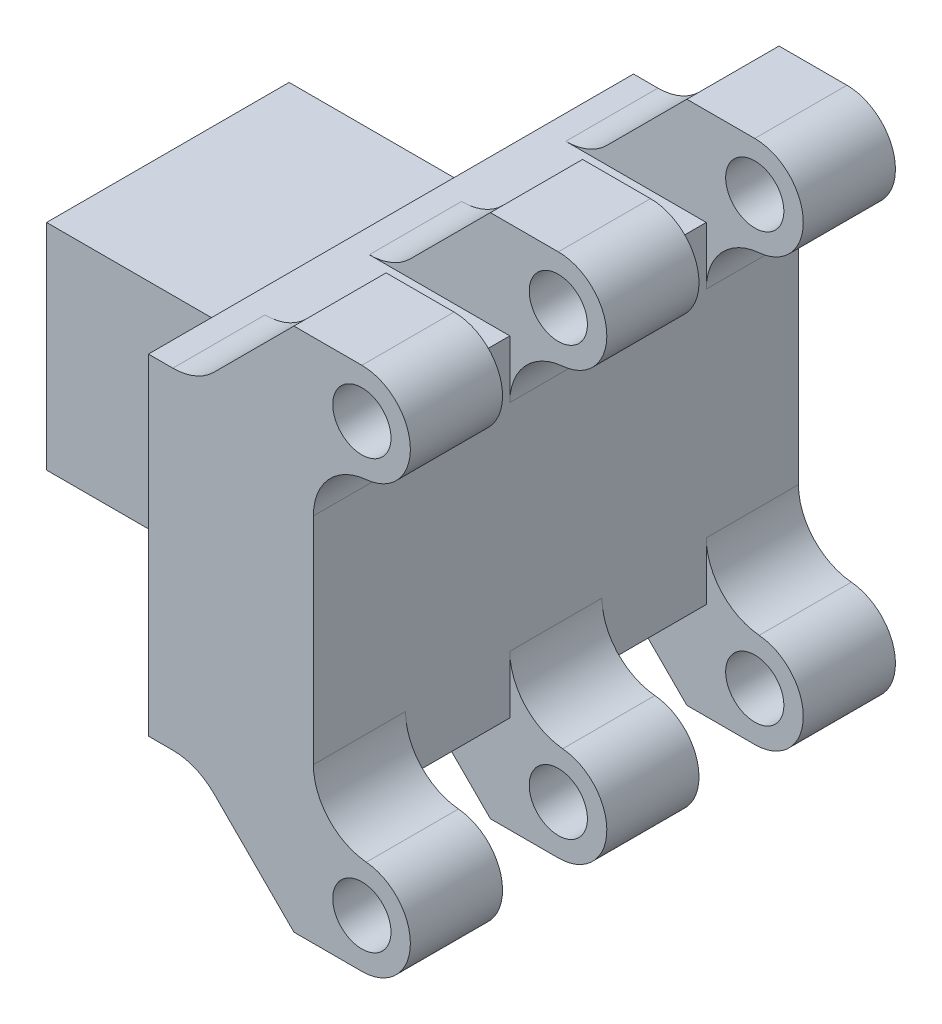
SolidWorks part; units mm, degrees
ref_plane "Front Plane" through (0, 0, 0) normal (0, 0, 1) x (1, 0, 0)
ref_plane "Top Plane" through (0, 0, 0) normal (0, 1, 0) x (1, 0, 0)
ref_plane "Right Plane" through (0, 0, 0) normal (1, 0, 0) x (0, 0, -1)
sketch "Sketch1" plane through (0, 0, 0) normal (1, 0, 0) x (0, 0, -1)
  line L1 (0, 0) -> (50, 0)
  line L2 (0, 0) -> (0, 34.11)
  line L3 (0, 34.11) -> (50, 34.11)
  line L4 (50, 0) -> (50, 34.11)
  dimension "D1" = 50
  dimension "D2" = 34.11
extrude "Boss-Extrude1" add sketch "Sketch1" along normal blind 20
sketch "Sketch2" plane through (0, 0, 0) normal (0, 0, 1) x (1, 0, 0)
  line L0 (20, 34.11) -> (0, 34.11) construction
  line L1 (20, 34.11) -> (20, 0) construction
  line L2 (20, 34.11) -> (25, 34.11)
  line L4 (25, 39.11) -> (25, 44.11) construction
  line L5 (25, 39.11) -> (25, 34.11) construction
  line L6 (18, 44.11) -> (8, 34.11)
  line L7 (8, 34.11) -> (20, 34.11)
  line L8 (20, 34.11) -> (40, 34.11) construction
  line L10 (18, 44.11) -> (25, 44.11)
  circle A0 centre (25, 39.11) radius 3
  arc A1 (25, 34.11) -> (25, 44.11) centre (25, 39.11) ccw
  dimension "D1" = 6
  dimension "D2" = 5
  dimension "D3" = 5
  dimension "D4" = 45
  dimension "D5" = 20
  dimension "D6" = 12
extrude "Boss-Extrude2" add sketch "Sketch2" against normal blind 9.5
pattern_linear "LPattern1" count 3 spacing 20.25 along (0, 0, -1) of "Boss-Extrude2"
ref_plane "Plane1" through (0, 17.055, 0) normal (0, 1, 0) x (1, 0, 0)
mirror "Mirror1" about plane through (0, 17.055, 0) normal (0, 1, 0) of "LPattern1"
sketch "Sketch3" plane through (0, 0, 0) normal (-1, 0, 0) x (0, 0, 1)
  line L0 (-50, 17.055) -> (0, 17.055) construction
  line L1 (-50, 0) -> (-50, 34.11) construction
  line L2 (0, 34.11) -> (0, 0) construction
  line L3 (-37.5, 17.055) -> (-12.5, 17.055) construction
  line L4 (-37.5, 2.055) -> (-37.5, 32.055)
  line L7 (-40.5, 2.055) -> (-40.5, 32.055)
  line L8 (-25, 34.11) -> (-25, 0) construction
  line L9 (-29.75, 34.11) -> (-20.25, 34.11) construction
  line L10 (0, 0) -> (-50, 0) construction
  line L12 (-12.5, 2.055) -> (-12.5, 32.055)
  line L13 (-12.5, 32.055) -> (-9.5, 32.055)
  line L14 (-9.5, 2.055) -> (-9.5, 32.055)
  line L15 (-40.5, 32.055) -> (-37.5, 32.055)
  line L16 (-40.5, 2.055) -> (-37.5, 2.055)
  line L18 (-12.5, 2.055) -> (-9.5, 2.055)
  circle A0 centre (-25, 17.055) radius 8
  point P11 (-25, 17.055)
  point P14 (-37.5, 17.055)
  point P15 (-37.5, 17.055)
  dimension "D1" = 16
  dimension "D2" = 25
  dimension "D3" = 30
  dimension "D4" = 3
extrude "Cut-Extrude1" cut sketch "Sketch3" against normal blind 10
sketch "Sketch4" plane through (0, 0, 0) normal (1, 0, 0) x (0, 0, -1)
  line L0 (0, 34.11) -> (0, 0) construction
  line L1 (50, 34.11) -> (0, 34.11)
  line L2 (50, 34.11) -> (50, 28.11)
  line L3 (46, 28.11) -> (4, 28.11)
  line L4 (0, 34.11) -> (0, 28.11)
  line L5 (50, 28.11) -> (50, 6)
  line L6 (50, 0) -> (0, 0)
  line L7 (50, 0) -> (50, 6)
  line L8 (46, 6) -> (4, 6)
  line L9 (0, 0) -> (0, 6)
  line L10 (46, 28.11) -> (46, 6)
  line L11 (0, 28.11) -> (0, 6)
  line L12 (4, 28.11) -> (4, 6)
  dimension "D1" = 6
  dimension "D2" = 6
  dimension "D3" = 4
  dimension "D4" = 4
extrude "Cut-Extrude2" cut sketch "Sketch4" along normal blind 3
fillet "Fillet1" radius 6 6 edges at (20, 0, -45.25) (20, 0, -25) (20, 0, -4.75) (20, 34.11, -45.25) (20, 34.11, -25) (20, 34.11, -4.75)
fillet "Fillet2" radius 6 6 edges at (8, 0, -25) (8, 0, -45.25) (8, 0, -4.75) (8, 34.11, -4.75) (8, 34.11, -45.25) (8, 34.11, -25)
sketch "Sketch5" plane through (0, 0, 0) normal (-1, 0, 0) x (0, 0, 1)
  line L4 (-12.5, 28.11) -> (-37.5, 28.11)
  line L5 (-37.5, 28.11) -> (-37.5, 6)
  line L6 (-37.5, 6) -> (-12.5, 6)
  line L7 (-12.5, 6) -> (-12.5, 28.11)
  line L8 (-12.5, 28.11) -> (-37.5, 28.11)
  line L9 (-37.5, 28.11) -> (-37.5, 6)
  line L10 (-37.5, 6) -> (-12.5, 6)
  line L11 (-12.5, 6) -> (-12.5, 28.11)
  circle A1 centre (-25, 17.055) radius 8 construction
  circle A2 centre (-25, 17.055) radius 8
  dimension "D1" = 0
extrude "Boss-Extrude3" add sketch "Sketch5" along normal blind 20
